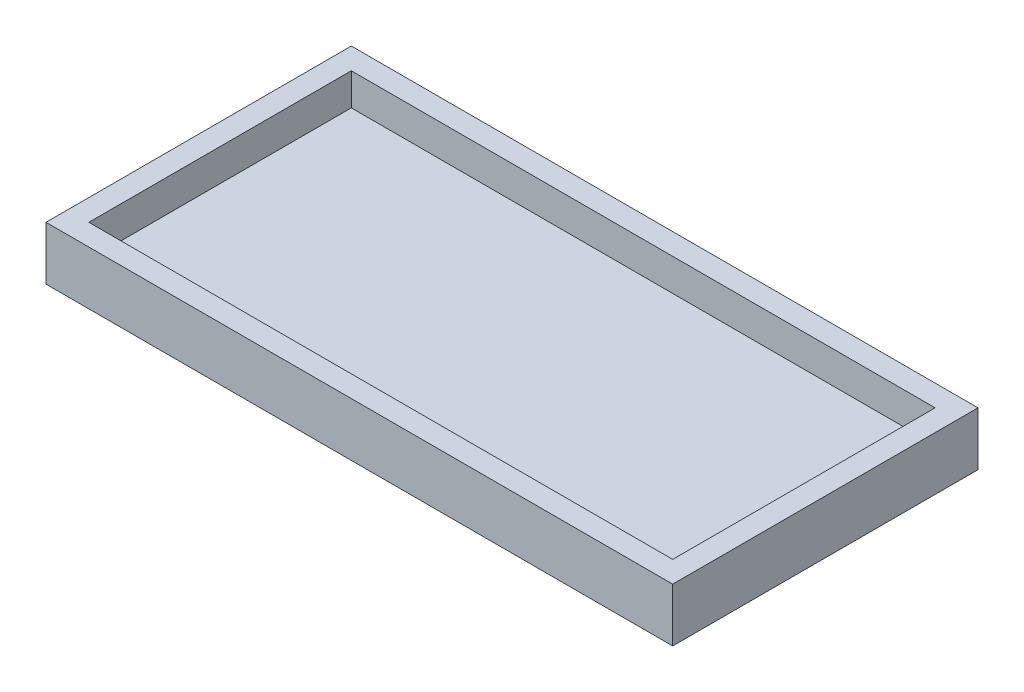
SolidWorks part; units mm, degrees
ref_plane "Front Plane" through (0, 0, 0) normal (0, 0, 1) x (1, 0, 0)
ref_plane "Top Plane" through (0, 0, 0) normal (0, 1, 0) x (1, 0, 0)
ref_plane "Right Plane" through (0, 0, 0) normal (1, 0, 0) x (0, 0, -1)
sketch "Sketch1" plane through (0, 0, 0) normal (0, 1, 0) x (1, 0, 0)
  line L1 (-27.25, -12.25) -> (27.25, -12.25)
  line L2 (-27.25, -12.25) -> (-27.25, 12.25)
  line L3 (-27.25, 12.25) -> (27.25, 12.25)
  line L4 (27.25, -12.25) -> (27.25, 12.25)
  line L5 (-27.25, -12.25) -> (27.25, 12.25) construction
  line L6 (-27.25, 12.25) -> (27.25, -12.25) construction
  point P0 (0, 0)
  dimension "D1" = 54.5
  dimension "D2" = 24.5
extrude "Boss-Extrude1" add sketch "Sketch1" along normal blind 2
sketch "Sketch2" plane through (0, 2, 0) normal (0, 1, 0) x (1, 0, 0)
  line L0 (29.25, 14.25) -> (-29.25, 14.25)
  line L1 (-29.25, 14.25) -> (-29.25, -14.25)
  line L2 (-29.25, -14.25) -> (29.25, -14.25)
  line L3 (29.25, -14.25) -> (29.25, 14.25)
  line L4 (27.25, -12.25) -> (27.25, 12.25)
  line L5 (27.25, 12.25) -> (-27.25, 12.25)
  line L6 (-27.25, 12.25) -> (-27.25, -12.25)
  line L7 (-27.25, -12.25) -> (27.25, -12.25)
  line L8 (27.25, -12.25) -> (27.25, 12.25)
  line L9 (27.25, 12.25) -> (-27.25, 12.25)
  line L10 (-27.25, 12.25) -> (-27.25, -12.25)
  line L11 (-27.25, -12.25) -> (27.25, -12.25)
  dimension "D1" = 0
  dimension "D2" = 2
extrude "Boss-Extrude2" add sketch "Sketch2" along normal blind 5 from surface starting at face at (0, 0, 0)
